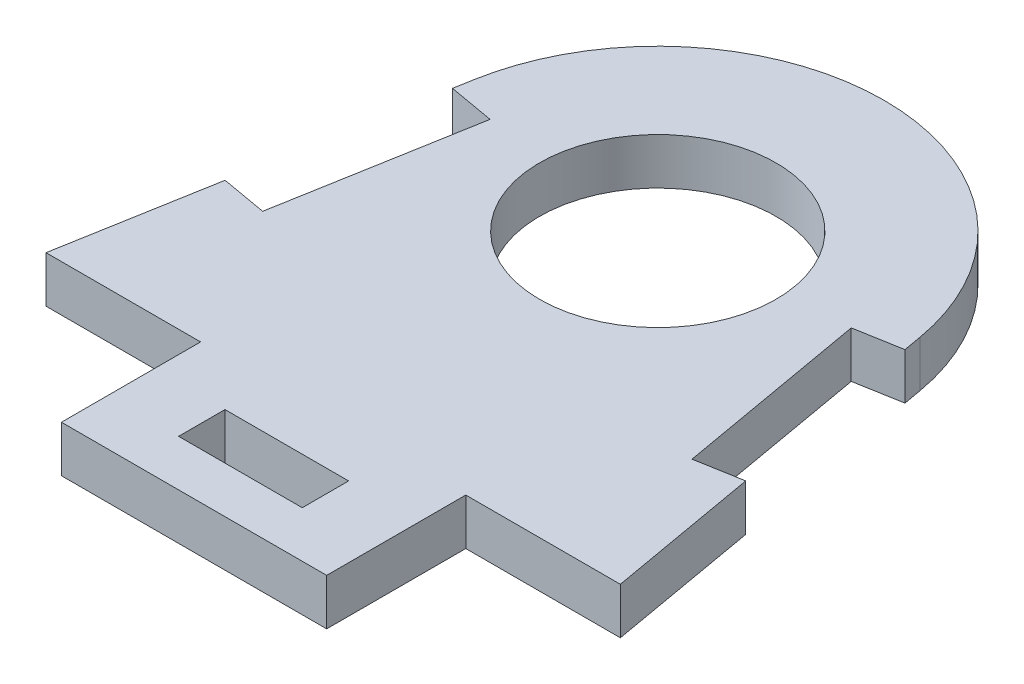
SolidWorks part; units mm, degrees
ref_plane "Front Plane" through (0, 0, 0) normal (0, 0, 1) x (1, 0, 0)
ref_plane "Top Plane" through (0, 0, 0) normal (0, 1, 0) x (1, 0, 0)
ref_plane "Right Plane" through (0, 0, 0) normal (1, 0, 0) x (0, 0, -1)
sketch "Sketch1" plane through (0, 0, 0) normal (0, 1, 0) x (1, 0, 0)
  line L0 (-18.5789, 0) -> (18.5789, 0)
  line L1 (18.5789, 0) -> (14.4274, 23.5439)
  line L2 (-18.5789, 0) -> (-14.4274, 23.5439)
  line L3 (14.6371, 22.3551) -> (16.8424, 9.8481)
  line L4 (14.6371, 22.3551) -> (11.6826, 21.8342)
  line L5 (16.8424, 9.8481) -> (13.888, 9.3271)
  line L6 (11.6826, 21.8342) -> (13.888, 9.3271)
  line L7 (-14.6371, 22.3551) -> (-16.8424, 9.8481)
  line L8 (-14.6371, 22.3551) -> (-11.6826, 21.8342)
  line L9 (-16.8424, 9.8481) -> (-13.888, 9.3271)
  line L10 (-11.6826, 21.8342) -> (-13.888, 9.3271)
  line L11 (-8.5789, 0) -> (-8.5789, -9)
  line L12 (-8.5789, -9) -> (8.5789, -9)
  line L13 (8.5789, -9) -> (8.5789, 0)
  line L14 (4, 0) -> (4, -3) construction
  line L15 (-4, -6) -> (4, -6)
  line L16 (-4, -6) -> (-4, -3)
  line L17 (-4, -3) -> (4, -3)
  line L18 (4, -6) -> (4, -3)
  line L19 (-4, -6) -> (4, -3) construction
  line L20 (-4, -3) -> (4, -6) construction
  line L21 (4, -6) -> (4, -9) construction
  circle A0 centre (0, 21) radius 7.65
  arc A1 (-14.4274, 23.5439) -> (14.4274, 23.5439) centre (0, 21) cw
  point P10 (0, 0)
  point P11 (0, 21)
  point P15 (0, -4.5)
  point P28 (0, -9)
  dimension "D2" = 15.3
  dimension "D3" = 7
  dimension "D1" = 21
  dimension "D4" = 80
  dimension "D5" = 3
  dimension "D6" = 12.7
  dimension "D7" = 10
  dimension "D8" = 10
  dimension "D9" = 3
  dimension "D10" = 10
  dimension "D11" = 8
extrude "Boss-Extrude1" add sketch "Sketch1" along normal mid plane 3 contours A1 L2 L8 L10 L9 L0 L1 L5 L6 L4 A0 | L12 L13 L0 L11 L18 L15 L16 L17 region at (-17.2035, 0, -4.8346) region at (0, 0, 0.1937)
ref_axis "Axis1" through (0, 0, -21) along (0, 1, 0)
